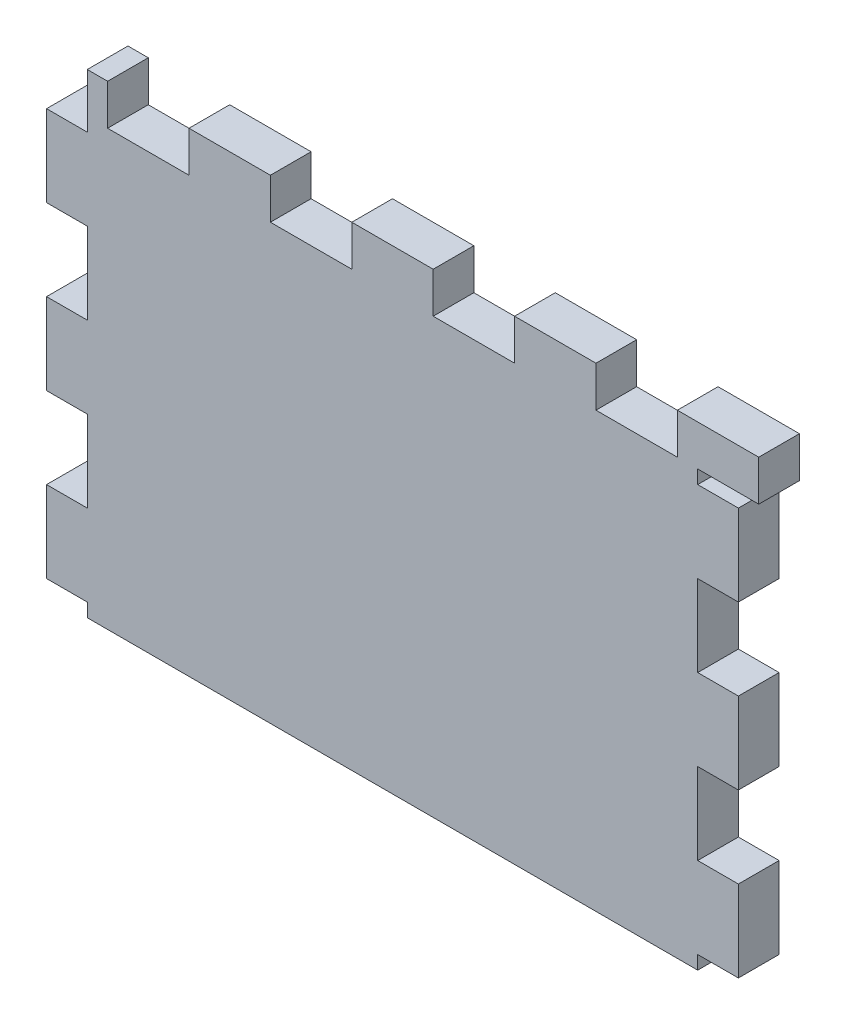
SolidWorks part; units mm, degrees
ref_plane "Front Plane" through (0, 0, 0) normal (0, 0, 1) x (1, 0, 0)
ref_plane "Top Plane" through (0, 0, 0) normal (0, 1, 0) x (1, 0, 0)
ref_plane "Right Plane" through (0, 0, 0) normal (1, 0, 0) x (0, 0, -1)
sketch "Sketch1" plane through (0, 0, 0) normal (0, 0, 1) x (1, 0, 0)
  line L1 (-22.5, 16) -> (22.5, 16)
  line L2 (-22.5, 16) -> (-22.5, -16)
  line L3 (-22.5, -16) -> (22.5, -16)
  line L4 (22.5, 16) -> (22.5, -16)
  line L5 (-22.5, 16) -> (22.5, -16) construction
  line L6 (-22.5, -16) -> (22.5, 16) construction
  point P0 (0, 0)
  dimension "D1" = 32
  dimension "D2" = 45
extrude "Boss-Extrude1" add sketch "Sketch1" along normal blind 3
sketch "Sketch2" plane through (-22.5, 0, 0) normal (-1, 0, 0) x (0, 0, 1)
  line L0 (0, 0) -> (3, 0) construction
  line L1 (0, 16) -> (0, -16) construction
  line L2 (3, 16) -> (3, -16) construction
  line L4 (3, 3) -> (0, 3)
  line L5 (3, 3) -> (3, -3)
  line L6 (3, -3) -> (0, -3)
  line L7 (0, 3) -> (0, -3)
  line L8 (3, 3) -> (0, -3) construction
  line L9 (3, -3) -> (0, 3) construction
  point P6 (1.5, 0)
  dimension "D1" = 6
extrude "Boss-Extrude2" add sketch "Sketch2" along normal blind 3
pattern_linear "LPattern1" count 2 spacing 12 along (0, -1, 0) count 2 spacing 12 along (0, 1, 0) of "Boss-Extrude2" pattern seed only yes
sketch "Sketch3" plane through (0, 16, 0) normal (0, 1, 0) x (1, 0, 0)
  line L0 (0, 0) -> (0, -3) construction
  line L1 (22.5, 0) -> (-22.5, 0) construction
  line L2 (22.5, -3) -> (-22.5, -3) construction
  line L4 (-3, 0) -> (3, 0)
  line L5 (-3, 0) -> (-3, -3)
  line L6 (-3, -3) -> (3, -3)
  line L7 (3, 0) -> (3, -3)
  line L8 (-3, 0) -> (3, -3) construction
  line L9 (-3, -3) -> (3, 0) construction
  point P6 (0, -1.5)
  dimension "D1" = 6
extrude "Boss-Extrude3" add sketch "Sketch3" along normal blind 3
pattern_linear "LPattern2" count 3 spacing 12 along (-1, 0, 0) count 3 spacing 12 along (1, 0, 0) of "Boss-Extrude3" pattern seed only yes
ref_plane "Plane1" through (0, 0, 0) normal (1, 0, 0) x (0, 0, -1)
mirror "Mirror1" about plane through (0, 0, 0) normal (1, 0, 0) of "LPattern1"
sketch "Sketch5" plane through (0, 0, 0) normal (0, 0, -1) x (-1, 0, 0)
  line L0 (21, 19) -> (27, 19) construction
  line L1 (27, 16) -> (22.5, 16)
  line L2 (27, 16) -> (27, 19)
  line L3 (27, 19) -> (22.5, 19)
  line L4 (22.5, 16) -> (22.5, 19)
  line L5 (27, 16) -> (22.5, 19) construction
  line L6 (27, 19) -> (22.5, 16) construction
  line L7 (22.5, 19) -> (22.5, 13) construction
  point P4 (24.75, 17.5)
extrude "Cut-Extrude1" cut sketch "Sketch5" against normal blind 3
